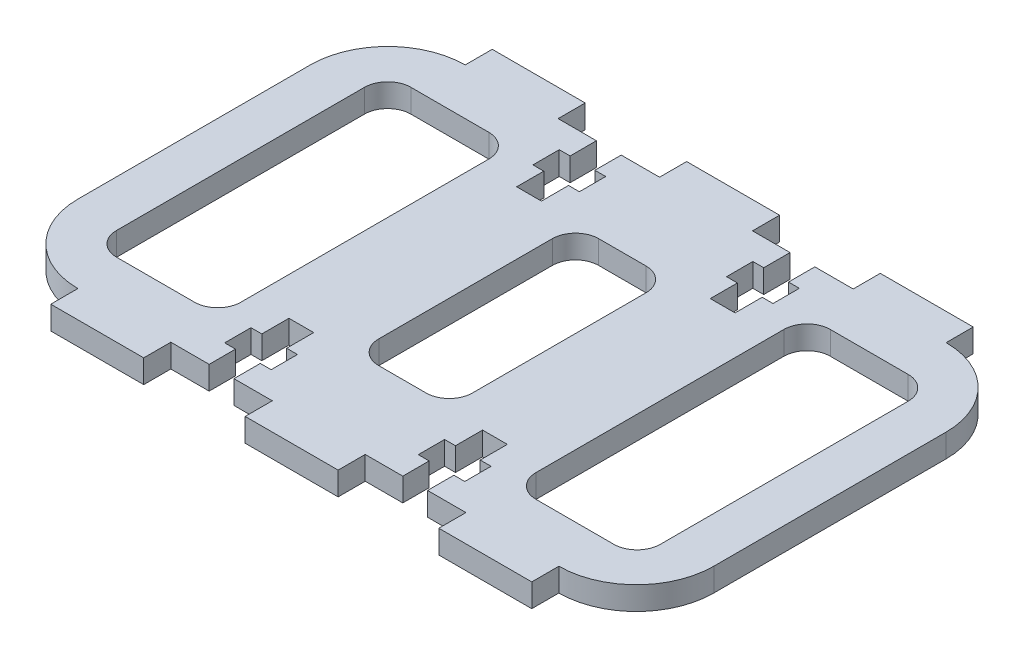
SolidWorks part; units mm, degrees
material "Thornel Mat VMA"
ref_plane "前视基准面" through (0, 0, 0) normal (0, 0, 1) x (1, 0, 0)
ref_plane "上视基准面" through (0, 0, 0) normal (0, 1, 0) x (1, 0, 0)
ref_plane "右视基准面" through (0, 0, 0) normal (1, 0, 0) x (0, 0, -1)
sketch "草图1" plane through (0, 0, 0) normal (0, 1, 0) x (1, 0, 0)
  line L0 (10, 0) -> (10, -3.5)
  line L1 (0, 0) -> (10, 0)
  line L2 (0, 0) -> (0, 50)
  line L3 (0, 50) -> (10, 50)
  line L4 (82.1, 0) -> (82.1, 50)
  line L5 (10, -3.5) -> (22, -3.5)
  line L6 (22, -3.5) -> (22, 0)
  line L7 (26.95, 0) -> (26.95, 3.4)
  line L8 (26.95, 3.4) -> (25.55, 3.4)
  line L9 (25.55, 3.4) -> (25.55, 6.8)
  line L10 (25.55, 6.8) -> (26.95, 6.8)
  line L11 (26.95, 6.8) -> (26.95, 10.3)
  line L12 (26.95, 10.3) -> (30.15, 10.3)
  line L13 (30.15, 10.3) -> (30.15, 6.8)
  line L14 (30.15, 6.8) -> (31.55, 6.8)
  line L15 (31.55, 6.8) -> (31.55, 3.4)
  line L16 (31.55, 3.4) -> (30.15, 3.4)
  line L17 (30.15, 3.4) -> (30.15, 0)
  line L18 (28.55, -0.9012) -> (28.55, 13.2859) construction
  line L19 (22, 0) -> (26.95, 0)
  line L20 (30.15, 0) -> (35.1, 0)
  line L21 (35.1, 0) -> (35.1, -3.5)
  line L22 (35.1, -3.5) -> (47.1, -3.5)
  line L23 (47.1, -3.5) -> (47.1, 0)
  line L24 (47.1, 0) -> (51.95, 0)
  line L25 (0, 25) -> (82.1, 25) construction
  line L26 (28.55, 50.9012) -> (28.55, 36.7141) construction
  line L27 (30.15, 46.6) -> (30.15, 50)
  line L28 (31.55, 46.6) -> (30.15, 46.6)
  line L29 (31.55, 43.2) -> (31.55, 46.6)
  line L30 (30.15, 43.2) -> (31.55, 43.2)
  line L31 (30.15, 39.7) -> (30.15, 43.2)
  line L32 (26.95, 39.7) -> (30.15, 39.7)
  line L33 (26.95, 43.2) -> (26.95, 39.7)
  line L34 (25.55, 43.2) -> (26.95, 43.2)
  line L35 (25.55, 46.6) -> (25.55, 43.2)
  line L36 (50.65, 3.4) -> (50.65, 6.8) [skipped]
  line L37 (50.65, 6.8) -> (52.05, 6.8) [skipped]
  line L38 (52.05, 6.8) -> (52.05, 10.3) [skipped]
  line L39 (56.65, 3.4) -> (55.25, 3.4) [skipped]
  line L40 (56.65, 6.8) -> (56.65, 3.4) [skipped]
  line L41 (55.25, 6.8) -> (56.65, 6.8) [skipped]
  line L42 (55.25, 10.3) -> (55.25, 6.8) [skipped]
  line L43 (52.05, 10.3) -> (55.25, 10.3) [skipped]
  line L44 (52.05, 0) -> (52.05, 3.4) [skipped]
  line L45 (55.25, 3.4) -> (55.25, 0) [skipped]
  line L46 (26.95, 46.6) -> (25.55, 46.6)
  line L47 (26.95, 50) -> (26.95, 46.6)
  line L48 (47.1, 53.5) -> (47.1, 50)
  line L49 (35.1, 53.5) -> (47.1, 53.5)
  line L50 (35.1, 50) -> (35.1, 53.5)
  line L51 (22, 53.5) -> (22, 50)
  line L52 (10, 53.5) -> (22, 53.5)
  line L53 (10, 50) -> (10, 53.5)
  line L54 (22, 50) -> (26.95, 50)
  line L55 (30.15, 50) -> (35.1, 50)
  line L56 (47.1, 50) -> (51.95, 50)
  line L57 (51.95, 0) -> (51.95, 3.4)
  line L58 (51.95, 3.4) -> (50.55, 3.4)
  line L59 (50.55, 3.4) -> (50.55, 6.8)
  line L60 (50.55, 6.8) -> (51.95, 6.8)
  line L61 (51.95, 6.8) -> (51.95, 10.3)
  line L62 (51.95, 10.3) -> (55.15, 10.3)
  line L63 (55.15, 10.3) -> (55.15, 6.8)
  line L64 (55.15, 6.8) -> (56.55, 6.8)
  line L65 (56.55, 6.8) -> (56.55, 3.4)
  line L66 (56.55, 3.4) -> (55.15, 3.4)
  line L67 (55.15, 3.4) -> (55.15, 0)
  line L68 (53.55, -0.9012) -> (53.55, 13.2859) construction
  line L69 (60.1, 0) -> (60.1, -3.5)
  line L70 (60.1, -3.5) -> (72.1, -3.5)
  line L71 (72.1, -3.5) -> (72.1, 0)
  line L72 (55.15, 46.6) -> (55.15, 50)
  line L73 (56.55, 46.6) -> (55.15, 46.6)
  line L74 (56.55, 43.2) -> (56.55, 46.6)
  line L75 (55.15, 43.2) -> (56.55, 43.2)
  line L76 (55.15, 39.7) -> (55.15, 43.2)
  line L77 (51.95, 39.7) -> (55.15, 39.7)
  line L78 (51.95, 43.2) -> (51.95, 39.7)
  line L79 (50.55, 43.2) -> (51.95, 43.2)
  line L80 (50.55, 46.6) -> (50.55, 43.2)
  line L81 (51.95, 46.6) -> (50.55, 46.6)
  line L82 (51.95, 50) -> (51.95, 46.6)
  line L83 (72.1, 53.5) -> (72.1, 50)
  line L84 (60.1, 53.5) -> (72.1, 53.5)
  line L85 (60.1, 50) -> (60.1, 53.5)
  line L86 (55.15, 50) -> (60.1, 50)
  line L87 (55.15, 0) -> (60.1, 0)
  line L88 (72.1, 0) -> (82.1, 0)
  line L89 (72.1, 50) -> (82.1, 50)
  dimension "D1" = 3.5
  dimension "D2" = 12
  dimension "D3" = 10
  dimension "D4" = 4.95
  dimension "D5" = 3.2
  dimension "D6" = 3.4
  dimension "D7" = 3.4
  dimension "D8" = 3.5
  dimension "D9" = 6
  dimension "D10" = 50
  dimension "D11" = 10
  dimension "D13" = 4.95
  dimension "D14" = 2
  dimension "D16" = 25
  dimension "D17" = 25
  dimension "D12" = 2
  dimension "D15" = 2
extrude "凸台-拉伸1" add sketch "草图1" along normal blind 3
fillet "圆角1" radius 10 4 edges at (0, 1.5, -50) (82.1, 1.5, -50) (82.1, 1.5, 0) (0, 1.5, 0)
sketch "草图2" plane through (0, 0, 0) normal (0, -1, 0) x (1, 0, 0)
  line L0 (41.1, -53.5) -> (41.1, 3.5) construction
  line L1 (35.05, -10.8) -> (47.15, -10.8)
  line L2 (35.05, -10.8) -> (35.05, -39.2)
  line L3 (35.05, -39.2) -> (47.15, -39.2)
  line L4 (47.15, -10.8) -> (47.15, -39.2)
  line L5 (6, -6) -> (22.05, -6)
  line L6 (6, -6) -> (6, -44)
  line L7 (6, -44) -> (22.05, -44)
  line L8 (22.05, -6) -> (22.05, -44)
  line L9 (47.1, -53.5) -> (35.1, -53.5) construction
  line L10 (35.1, 3.5) -> (47.1, 3.5) construction
  line L11 (31.55, -6.8) -> (31.55, -3.4) construction
  line L12 (30.15, -6.8) -> (31.55, -6.8) construction
  line L13 (31.55, -43.2) -> (30.15, -43.2) construction
  line L14 (26.95, -50) -> (22, -50) construction
  line L15 (0, -40) -> (0, -10) construction
  line L16 (22, 0) -> (26.95, 0) construction
  line L17 (25.55, -43.2) -> (25.55, -46.6) construction
  line L18 (60.15, -6) -> (60.15, -44)
  line L19 (76.2, -44) -> (60.15, -44)
  line L20 (76.2, -6) -> (76.2, -44)
  line L21 (76.2, -6) -> (60.15, -6)
  dimension "D1" = 3.5
  dimension "D2" = 4
  dimension "D3" = 4
  dimension "D4" = 6
  dimension "D5" = 6
  dimension "D6" = 6
  dimension "D7" = 3.5
extrude "切除-拉伸1" cut sketch "草图2" against normal through all
fillet "圆角2" radius 3 12 edges at (76.2, 1.5, -44) (60.15, 1.5, -44) (60.15, 1.5, -6) (76.2, 1.5, -6) (47.15, 1.5, -10.8) (47.15, 1.5, -39.2) (35.05, 1.5, -39.2) (35.05, 1.5, -10.8) (6, 1.5, -6) (22.05, 1.5, -6) (22.05, 1.5, -44) (6, 1.5, -44)
